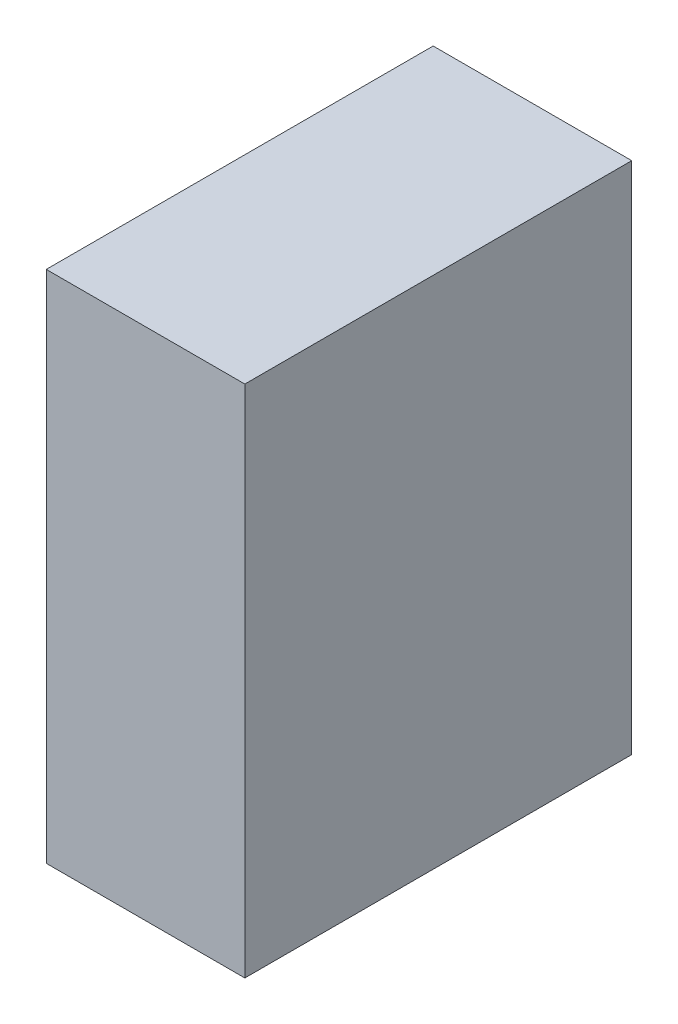
SolidWorks part; units mm, degrees
ref_plane "Front Plane" through (0, 0, 0) normal (0, 0, 1) x (1, 0, 0)
ref_plane "Top Plane" through (0, 0, 0) normal (0, 1, 0) x (1, 0, 0)
ref_plane "Right Plane" through (0, 0, 0) normal (1, 0, 0) x (0, 0, -1)
sketch "Sketch1" plane through (0, 0, 0) normal (0, 1, 0) x (1, 0, 0)
  line L1 (-19.685, -38.354) -> (19.685, -38.354)
  line L2 (-19.685, -38.354) -> (-19.685, 38.354)
  line L3 (-19.685, 38.354) -> (19.685, 38.354)
  line L4 (19.685, -38.354) -> (19.685, 38.354)
  line L5 (-19.685, -38.354) -> (19.685, 38.354) construction
  line L6 (-19.685, 38.354) -> (19.685, -38.354) construction
  point P0 (0, 0)
  dimension "D1" = 76.708
  dimension "D2" = 39.37
extrude "Boss-Extrude1" add sketch "Sketch1" along normal blind 50.9905 and the other way blind 50.9905
